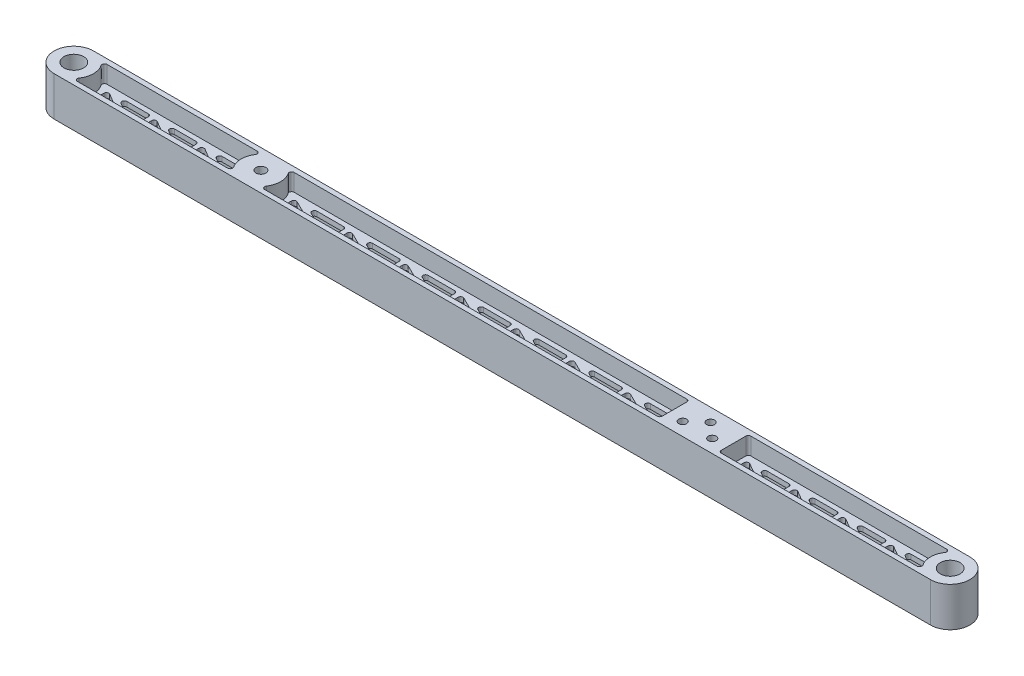
SolidWorks part; units mm, degrees
ref_plane "Front Plane" through (0, 0, 0) normal (0, 0, 1) x (1, 0, 0)
ref_plane "Top Plane" through (0, 0, 0) normal (0, 1, 0) x (1, 0, 0)
ref_plane "Right Plane" through (0, 0, 0) normal (1, 0, 0) x (0, 0, -1)
sketch "Sketch2" plane through (0, 0, 0) normal (0, 1, 0) x (1, 0, 0)
  line L0 (0, 0) -> (120.65, 0)
  line L1 (0, 0) -> (565.15, 0)
  line L2 (0, 0) -> (0, 25.4) construction
  line L3 (0, 25.4) -> (565.15, 25.4)
  line L4 (565.15, 0) -> (565.15, 25.4) construction
  line L5 (120.65, 0) -> (120.65, 25.4) construction
  circle A0 centre (120.65, 12.7) radius 12.7
  arc A1 (565.15, 25.4) -> (565.15, 0) centre (565.15, 12.7) cw
  circle A2 centre (120.65, 12.7) radius 3.175
  circle A3 centre (565.15, 12.7) radius 6.35
  arc A4 (0, 25.4) -> (0, 0) centre (0, 12.7) ccw
  circle A5 centre (0, 12.7) radius 6.35
  dimension "D4" = 6.35
  dimension "D5" = 12.7
  dimension "D6" = 12.7
  dimension "D1" = 565.15
  dimension "D2" = 25.4
  dimension "D3" = 120.65
extrude "Boss-Extrude1" add sketch "Sketch2" along normal blind 25.4 contours A0 L3 L2 L0 | A0 A2 | A1 L3 A0 L1 A3 region at (52.5215, 0, -12.7) region at (350.4658, 0, -12.7) region at (108.3092, 0, -12.7)
sketch "Sketch12" plane through (0, 0, -25.4) normal (0, 0, -1) x (-1, 0, 0)
  line L0 (-565.15, 25.4) -> (-425.45, 25.4)
  line L1 (0, 25.4) -> (-565.15, 25.4) construction
  line L2 (-387.35, 0) -> (-425.45, 0)
  line L3 (-425.45, 25.4) -> (-425.45, 0)
  line L5 (-387.35, 0) -> (-387.35, 25.4)
  line L6 (-425.45, 25.4) -> (-387.35, 25.4)
  line L7 (0, 0) -> (-565.15, 0) construction
  dimension "D1" = 139.7
  dimension "D2" = 38.1
sketch "Sketch13" plane through (0, 25.4, 0) normal (0, 1, 0) x (1, 0, 0)
  line L0 (565.15, 25.4) -> (565.15, 0) construction
  line L1 (0, 25.4) -> (0, 0) construction
  line L2 (565.15, 25.4) -> (565.15, 0) construction
  line L3 (565.15, 22.225) -> (0, 22.225)
  line L4 (0, 3.175) -> (565.15, 3.175)
  line L5 (565.15, 25.4) -> (425.45, 25.4) construction
  line L6 (0, 0) -> (565.15, 0) construction
  line L7 (12.7, 12.7) -> (15.875, 12.7) construction
  line L8 (15.875, 19.05) -> (15.875, 6.35)
  line L9 (15.875, 6.35) -> (37.189, 6.35)
  line L10 (37.189, 6.35) -> (15.875, 19.05)
  line L11 (22.0777, 19.05) -> (43.3917, 6.35)
  line L12 (43.3917, 6.35) -> (43.3917, 19.05)
  line L13 (43.3917, 19.05) -> (22.0777, 19.05)
  line L14 (46.5667, 19.05) -> (46.5667, 6.35)
  line L15 (46.5667, 6.35) -> (67.8806, 6.35)
  line L16 (67.8806, 6.35) -> (46.5667, 19.05)
  line L17 (52.7694, 19.05) -> (74.0833, 6.35)
  line L18 (74.0833, 6.35) -> (74.0833, 19.05)
  line L19 (74.0833, 19.05) -> (52.7694, 19.05)
  line L20 (43.3917, 12.7) -> (46.5667, 12.7) construction
  line L21 (77.2583, 19.05) -> (77.2583, 6.35)
  line L22 (77.2583, 6.35) -> (98.5723, 6.35)
  line L23 (98.5723, 6.35) -> (77.2583, 19.05)
  line L24 (83.461, 19.05) -> (104.775, 6.35)
  line L25 (104.775, 6.35) -> (104.775, 19.05)
  line L26 (104.775, 19.05) -> (83.461, 19.05)
  line L27 (74.0833, 12.7) -> (77.2583, 12.7) construction
  line L28 (107.95, 12.7) -> (104.775, 12.7) construction
  line L29 (133.35, 12.7) -> (136.525, 12.7) construction
  line L30 (136.525, 19.05) -> (136.525, 6.35)
  line L31 (136.525, 6.35) -> (162.0538, 6.35)
  line L32 (162.0538, 6.35) -> (136.525, 19.05)
  line L33 (143.6533, 19.05) -> (169.1821, 6.35)
  line L34 (169.1821, 6.35) -> (169.1821, 19.05)
  line L35 (169.1821, 19.05) -> (143.6533, 19.05)
  line L36 (387.35, 25.4) -> (387.35, 0)
  line L37 (425.45, 25.4) -> (387.35, 25.4) construction
  line L38 (387.35, 0) -> (425.45, 0)
  line L39 (425.45, 0) -> (425.45, 25.4)
  line L40 (387.35, 25.4) -> (425.45, 25.4) construction
  line L41 (425.45, 25.4) -> (387.35, 25.4)
  line L42 (172.3571, 19.05) -> (172.3571, 6.35)
  line L43 (172.3571, 6.35) -> (197.886, 6.35)
  line L44 (197.886, 6.35) -> (172.3571, 19.05)
  line L45 (179.4855, 19.05) -> (205.0143, 6.35)
  line L46 (205.0143, 6.35) -> (205.0143, 19.05)
  line L47 (205.0143, 19.05) -> (179.4855, 19.05)
  line L48 (169.1821, 12.7) -> (172.3571, 12.7) construction
  line L49 (208.1893, 19.05) -> (208.1893, 6.35)
  line L50 (208.1893, 6.35) -> (233.7181, 6.35)
  line L51 (233.7181, 6.35) -> (208.1893, 19.05)
  line L52 (215.3176, 19.05) -> (240.8464, 6.35)
  line L53 (240.8464, 6.35) -> (240.8464, 19.05)
  line L54 (240.8464, 19.05) -> (215.3176, 19.05)
  line L55 (205.0143, 12.7) -> (208.1893, 12.7) construction
  line L56 (244.0214, 19.05) -> (244.0214, 6.35)
  line L57 (244.0214, 6.35) -> (269.5502, 6.35)
  line L58 (269.5502, 6.35) -> (244.0214, 19.05)
  line L59 (251.1498, 19.05) -> (276.6786, 6.35)
  line L60 (276.6786, 6.35) -> (276.6786, 19.05)
  line L61 (276.6786, 19.05) -> (251.1498, 19.05)
  line L62 (240.8464, 12.7) -> (244.0214, 12.7) construction
  line L63 (279.8536, 19.05) -> (279.8536, 6.35)
  line L64 (279.8536, 6.35) -> (305.3824, 6.35)
  line L65 (305.3824, 6.35) -> (279.8536, 19.05)
  line L66 (286.9819, 19.05) -> (312.5107, 6.35)
  line L67 (312.5107, 6.35) -> (312.5107, 19.05)
  line L68 (312.5107, 19.05) -> (286.9819, 19.05)
  line L69 (276.6786, 12.7) -> (279.8536, 12.7) construction
  line L70 (315.6857, 19.05) -> (315.6857, 6.35)
  line L71 (315.6857, 6.35) -> (341.2145, 6.35)
  line L72 (341.2145, 6.35) -> (315.6857, 19.05)
  line L73 (322.814, 19.05) -> (348.3429, 6.35)
  line L74 (348.3429, 6.35) -> (348.3429, 19.05)
  line L75 (348.3429, 19.05) -> (322.814, 19.05)
  line L76 (312.5107, 12.7) -> (315.6857, 12.7) construction
  line L77 (351.5179, 19.05) -> (351.5179, 6.35)
  line L78 (351.5179, 6.35) -> (377.0467, 6.35)
  line L79 (377.0467, 6.35) -> (351.5179, 19.05)
  line L80 (358.6462, 19.05) -> (384.175, 6.35)
  line L81 (384.175, 6.35) -> (384.175, 19.05)
  line L82 (384.175, 19.05) -> (358.6462, 19.05)
  line L83 (348.3429, 12.7) -> (351.5179, 12.7) construction
  line L84 (425.45, 12.7) -> (428.625, 12.7) construction
  line L85 (428.625, 19.05) -> (428.625, 6.35)
  line L86 (428.625, 6.35) -> (450.1567, 6.35)
  line L87 (450.1567, 6.35) -> (428.625, 19.05)
  line L88 (434.8745, 19.05) -> (456.4062, 6.35)
  line L89 (456.4062, 6.35) -> (456.4062, 19.05)
  line L90 (456.4062, 19.05) -> (434.8745, 19.05)
  line L91 (459.5812, 19.05) -> (459.5812, 6.35)
  line L92 (459.5812, 6.35) -> (481.113, 6.35)
  line L93 (481.113, 6.35) -> (459.5812, 19.05)
  line L94 (465.8308, 19.05) -> (487.3625, 6.35)
  line L95 (487.3625, 6.35) -> (487.3625, 19.05)
  line L96 (487.3625, 19.05) -> (465.8308, 19.05)
  line L97 (456.4062, 12.7) -> (459.5812, 12.7) construction
  line L98 (490.5375, 19.05) -> (490.5375, 6.35)
  line L99 (490.5375, 6.35) -> (512.0692, 6.35)
  line L100 (512.0692, 6.35) -> (490.5375, 19.05)
  line L101 (496.787, 19.05) -> (518.3187, 6.35)
  line L102 (518.3187, 6.35) -> (518.3187, 19.05)
  line L103 (518.3187, 19.05) -> (496.787, 19.05)
  line L104 (487.3625, 12.7) -> (490.5375, 12.7) construction
  line L105 (521.4937, 19.05) -> (521.4937, 6.35)
  line L106 (521.4937, 6.35) -> (543.0255, 6.35)
  line L107 (543.0255, 6.35) -> (521.4937, 19.05)
  line L108 (527.7433, 19.05) -> (549.275, 6.35)
  line L109 (549.275, 6.35) -> (549.275, 19.05)
  line L110 (549.275, 19.05) -> (527.7433, 19.05)
  line L111 (518.3187, 12.7) -> (521.4937, 12.7) construction
  line L112 (387.35, 12.7) -> (425.45, 12.7) construction
  line L113 (565.15, 12.7) -> (552.45, 12.7) construction
  line L114 (552.45, 12.7) -> (552.45, 25.4) construction
  line L115 (552.45, 25.4) -> (552.45, 3.175) construction
  line L116 (406.4, 25.4) -> (406.4, 0) construction
  line L117 (396.875, 25.4) -> (396.875, 0) construction
  line L118 (415.925, 0) -> (415.925, 25.4) construction
  line L119 (387.35, 16.9333) -> (425.45, 16.9333) construction
  line L120 (387.35, 8.4667) -> (425.45, 8.4667) construction
  circle A0 centre (565.15, 12.7) radius 12.7
  circle A1 centre (120.65, 12.7) radius 12.7
  circle A2 centre (0, 12.7) radius 12.7
  point P164 (406.4, 16.9333)
  dimension "D1" = 25.4
  dimension "D9" = 3.175
  dimension "D30" = 8.4667
  dimension "D2" = 3.175
  dimension "D3" = 3.175
  dimension "D4" = 3.175
  dimension "D5" = 3.175
  dimension "D6" = 3.175
  dimension "D7" = 3.175
  dimension "D10" = 3.175
  dimension "D11" = 3.175
  dimension "D12" = 3.175
  dimension "D13" = 3.175
  dimension "D14" = 3.175
  dimension "D15" = 139.7
  dimension "D16" = 38.1
  dimension "D17" = 7
  dimension "D18" = 3.175
  dimension "D19" = 3.175
  dimension "D20" = 3.175
  dimension "D21" = 3.175
  dimension "D22" = 3.175
  dimension "D23" = 3.175
  dimension "D25" = 3.175
  dimension "D26" = 3.175
  dimension "D27" = 9.525
  dimension "D28" = 9.525
  dimension "D29" = 8.4667
  dimension "D8" = 3
  dimension "D24" = 4
extrude "Cut-Extrude2" cut sketch "Sketch13" against normal through all contours L109 L110 L108 | L106 L107 L105 | L102 L103 L101 | L99 L100 L98 | L92 L93 L91 | L89 L90 L88 | L86 L87 L85 | L78 L79 L77 | L81 L82 L80 | L74 L75 L73 | L71 L72 L70 | L67 L68 L66 | L64 L65 L63 | L60 L61 L59 | L57 L58 L56 | L53 L54 L52 | L50 L51 L49 | L46 L47 L45 | L43 L44 L42 | L34 L35 L33 | L31 L32 L30 | L25 L26 L24 | L22 L23 L21 | L18 L19 L17 | L15 L16 L14 | L12 L13 L11 | L9 L10 L8 | L96 L94 L95 region at (22.9797, 25.4, -10.5833) region at (36.287, 25.4, -14.8167) region at (53.6713, 25.4, -10.5833) region at (66.9787, 25.4, -14.8167) region at (84.363, 25.4, -10.5833) region at (97.6703, 25.4, -14.8167) region at (145.0346, 25.4, -10.5833) region at (160.6725, 25.4, -14.8167) region at (180.8667, 25.4, -10.5833) region at (196.5047, 25.4, -14.8167) region at (216.6989, 25.4, -10.5833) region at (232.3368, 25.4, -14.8167) region at (252.531, 25.4, -10.5833) region at (268.169, 25.4, -14.8167) region at (288.3632, 25.4, -10.5833) region at (304.0011, 25.4, -14.8167) region at (324.1953, 25.4, -10.5833) region at (339.8333, 25.4, -14.8167) region at (360.0275, 25.4, -10.5833) region at (375.6654, 25.4, -14.8167) region at (435.8022, 25.4, -10.5833) region at (449.229, 25.4, -14.8167) region at (466.7585, 25.4, -10.5833) region at (497.7147, 25.4, -10.5833) region at (511.1415, 25.4, -14.8167) region at (528.671, 25.4, -10.5833) region at (542.0978, 25.4, -14.8167)
extrude "Cut-Extrude3" cut sketch "Sketch13<4>" against normal blind 11.1125 contours A2 L4 A1 L3 L10 L9 L8 L13 L12 L11 L16 L15 L14 L19 L18 L17 L23 L22 L21 L26 L25 L24 | A1 L4 L36 L3 L32 L31 L30 L35 L34 L33 L44 L43 L42 L47 L46 L45 L51 L50 L49 L54 L53 L52 L58 L57 L56 L61 L60 L59 L65 L64 L63 L68 L67 L66 L72 L71 L70 L75 L74 | A0 L3 L39 L4 L87 L86 L85 L90 L89 L88 L93 L92 L91 L96 L95 L94 L100 L99 L98 L103 L102 L101 L107 L106 L105 L110 L109 L108 region at (490.155, 25.4, -12.7) region at (259.1074, 25.4, -12.7) region at (60.325, 25.4, -12.7)
sketch "Sketch13<4>" plane through (0, 25.4, 0) normal (0, 1, 0) x (1, 0, 0) same geometry as "Sketch13"
ref_plane "Plane1" through (0, 12.7, 0) normal (0, -1, 0) x (-1, 0, 0)
mirror "Mirror1" about plane through (0, 12.7, 0) normal (0, -1, 0) of "Cut-Extrude3"
fillet "Fillet1" radius 1.5875 108 edges at (104.775, 12.7, -19.05) (83.461, 12.7, -19.05) (98.5723, 12.7, -6.35) (77.2583, 12.7, -6.35) (77.2583, 12.7, -19.05) (74.0833, 12.7, -19.05) (74.0833, 12.7, -6.35) (52.7694, 12.7, -19.05) (67.8806, 12.7, -6.35) (46.5667, 12.7, -6.35) (46.5667, 12.7, -19.05) (43.3917, 12.7, -19.05) (43.3917, 12.7, -6.35) (22.0777, 12.7, -19.05) (37.189, 12.7, -6.35) (15.875, 12.7, -6.35) (15.875, 12.7, -19.05) (104.775, 12.7, -6.35) (384.175, 12.7, -19.05) (358.6462, 12.7, -19.05) (377.0467, 12.7, -6.35) (351.5179, 12.7, -6.35) (351.5179, 12.7, -19.05) (348.3429, 12.7, -19.05) (348.3429, 12.7, -6.35) (322.814, 12.7, -19.05) (341.2145, 12.7, -6.35) (315.6857, 12.7, -6.35) (315.6857, 12.7, -19.05) (312.5107, 12.7, -19.05) (312.5107, 12.7, -6.35) (286.9819, 12.7, -19.05) (305.3824, 12.7, -6.35) (279.8536, 12.7, -6.35) (279.8536, 12.7, -19.05) (276.6786, 12.7, -19.05) (276.6786, 12.7, -6.35) (251.1498, 12.7, -19.05) (269.5502, 12.7, -6.35) (244.0214, 12.7, -6.35) (244.0214, 12.7, -19.05) (240.8464, 12.7, -19.05) (240.8464, 12.7, -6.35) (215.3176, 12.7, -19.05) (233.7181, 12.7, -6.35) (208.1893, 12.7, -6.35) (208.1893, 12.7, -19.05) (205.0143, 12.7, -19.05) (205.0143, 12.7, -6.35) (179.4855, 12.7, -19.05) (197.886, 12.7, -6.35) (172.3571, 12.7, -6.35) (172.3571, 12.7, -19.05) (169.1821, 12.7, -19.05) (169.1821, 12.7, -6.35) (143.6533, 12.7, -19.05) (162.0538, 12.7, -6.35) (136.525, 12.7, -6.35) (136.525, 12.7, -19.05) (384.175, 12.7, -6.35) (112.2497, 5.5562, -22.225) (112.2497, 5.5562, -3.175) (8.4003, 5.5562, -3.175) (8.4003, 5.5562, -22.225) (387.35, 5.5562, -22.225) (129.0503, 5.5562, -3.175) (129.0503, 5.5562, -22.225) (387.35, 5.5562, -3.175) (425.45, 19.8438, -22.225) (425.45, 19.8438, -3.175) (556.7497, 19.8438, -3.175) (112.2497, 19.8438, -3.175) (112.2497, 19.8438, -22.225) (8.4003, 19.8438, -22.225) (8.4003, 19.8438, -3.175) (387.35, 19.8438, -3.175) (387.35, 19.8438, -22.225) (129.0503, 19.8438, -22.225) (129.0503, 19.8438, -3.175) (556.7497, 19.8438, -22.225) (549.275, 12.7, -6.35) (527.7433, 12.7, -19.05) (543.0255, 12.7, -6.35) (521.4937, 12.7, -6.35) (521.4937, 12.7, -19.05) (518.3187, 12.7, -19.05) (518.3187, 12.7, -6.35) (496.787, 12.7, -19.05) (512.0692, 12.7, -6.35) (490.5375, 12.7, -6.35) (490.5375, 12.7, -19.05) (487.3625, 12.7, -19.05) (487.3625, 12.7, -6.35) (465.8308, 12.7, -19.05) (481.113, 12.7, -6.35) (459.5812, 12.7, -6.35) (459.5812, 12.7, -19.05) (456.4062, 12.7, -19.05) (456.4062, 12.7, -6.35) (434.8745, 12.7, -19.05) (450.1567, 12.7, -6.35) (428.625, 12.7, -6.35) (428.625, 12.7, -19.05) (549.275, 12.7, -19.05) (556.7497, 5.5562, -22.225) (425.45, 5.5562, -22.225) (425.45, 5.5562, -3.175) (556.7497, 5.5562, -3.175)
hole_wizard "1/4-20 Tapped Hole1" positions "3DSketch1" profile "Sketch14" tap size "1/4-20" standard "ANSI Inch"
sketch3d "3DSketch1"
  line L0 (396.875, 25.4, -25.4) -> (396.875, 25.4, 0) construction
  line L1 (387.35, 25.4, -8.4667) -> (425.45, 25.4, -8.4667) construction
  line L3 (415.925, 25.4, 0) -> (415.925, 25.4, -25.4) construction
  point P0 (396.875, 25.4, -8.4667)
  point P10 (415.925, 25.4, -8.4667)
  point P14 (406.4, 25.4, -16.9333)
sketch "Sketch14" plane through (396.875, 25.4, -8.4667) normal (1, 0, 0) x (0, 0, 1)
  line L0 (0, 0) -> (0, 20.5838)
  line L1 (0, 20.5838) -> (2.5527, 19.05)
  line L2 (2.5527, 19.05) -> (2.5527, 0)
  line L5 (2.5527, 0) -> (0, 0)
  line L10 (0, 20.5838) -> (-2.5527, 19.05) construction
  line L11 (0, -6.35) -> (0, 107.95) construction
  dimension "Tap Drill Dia." = 5.1054
  dimension "Tap Drill Depth" = 19.05
  dimension "Drill Angle" = 118
cosmetic thread "Hole Thread1" parameters "D1"=12.7, "D2"=6.35
cosmetic thread "Hole Thread2" parameters "D1"=12.7, "D2"=6.35
cosmetic thread "Hole Thread4" parameters "D1"=12.7, "D2"=6.35
